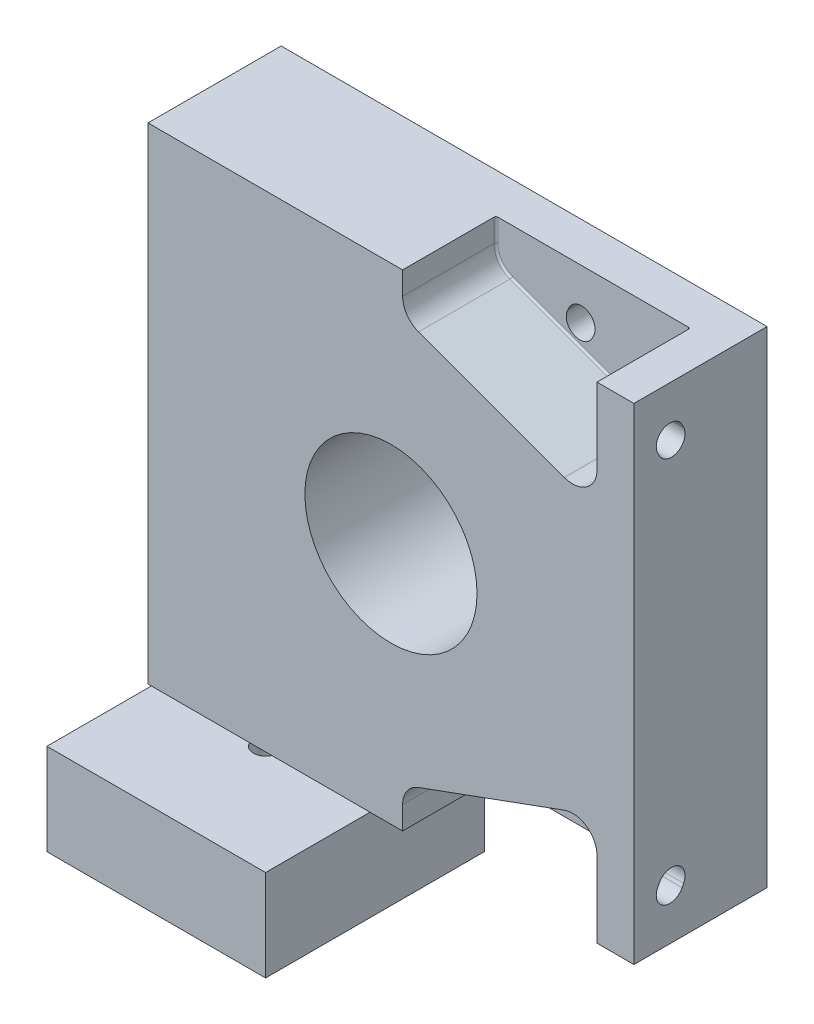
SolidWorks part; units mm, degrees
ref_plane "Front" through (0, 0, 0) normal (0, 0, 1) x (1, 0, 0)
ref_plane "Top" through (0, 0, 0) normal (0, 1, 0) x (1, 0, 0)
ref_plane "Right" through (0, 0, 0) normal (1, 0, 0) x (0, 0, -1)
sketch "Sketch2" plane through (0, 0, 0) normal (0, 0, 1) x (1, 0, 0)
  line L0 (-63.5, 63.5) -> (63.5, -63.5) construction
  line L1 (-63.5, 63.5) -> (63.5, 63.5)
  line L2 (-63.5, 63.5) -> (-63.5, -63.5)
  line L3 (-63.5, -63.5) -> (63.5, -63.5)
  line L4 (63.5, 63.5) -> (63.5, -63.5)
  dimension "D1" = 127
  dimension "D2" = 127
extrude "HOUSING" add sketch "Sketch2" along normal blind 39.5
ref_plane "Plane1" through (0, 0, 48.26) normal (0, 0, 1) x (1, 0, 0)
sketch "Sketch3" plane through (0, 0, 48.26) normal (0, 0, 1) x (1, 0, 0)
  circle A0 centre (0, 0) radius 22.5
  dimension "D1" = 45
sketch "Sketch4" plane through (0, 0, 39.5) normal (0, 0, 1) x (1, 0, 0)
  circle A0 centre (0, 0) radius 45.974
  dimension "D1" = 91.948
extrude "Cut-Extrude2" cut sketch "Sketch4" against normal blind 4.698 flip side to cut
sketch "Sketch8" plane through (0, 0, 34.802) normal (0, 0, 1) x (1, 0, 0)
  line L0 (3.048, -63.5) -> (3.048, -57.528)
  line L1 (-63.5, -63.5) -> (63.5, -63.5) construction
  line L2 (7.2207, -51.5629) -> (45.3207, -37.6564)
  line L3 (53.848, -43.6215) -> (53.848, -63.5)
  line L4 (-63.5, 63.5) -> (-63.5, -63.5) construction
  line L5 (3.048, -63.5) -> (53.848, -63.5)
  line L6 (0, 0) -> (83.0961, 0) construction
  line L7 (3.048, 63.5) -> (53.848, 63.5)
  line L8 (53.848, 43.6215) -> (53.848, 63.5)
  line L9 (7.2207, 51.5629) -> (45.3207, 37.6564)
  line L10 (3.048, 63.5) -> (3.048, 57.528)
  line L11 (53.848, -51.1628) -> (53.848, -17.132) construction
  line L12 (3.048, -53.086) -> (67.489, -29.5651) construction
  line L13 (3.048, -61.8074) -> (3.048, -48.2133) construction
  arc A0 (3.048, -57.528) -> (7.2207, -51.5629) centre (9.398, -57.528) cw
  arc A1 (45.3207, -37.6564) -> (53.848, -43.6215) centre (47.498, -43.6215) cw
  arc A2 (45.3207, 37.6564) -> (53.848, 43.6215) centre (47.498, 43.6215) ccw
  arc A3 (3.048, 57.528) -> (7.2207, 51.5629) centre (9.398, 57.528) ccw
  point P27 (53.848, -34.544)
  point P30 (3.048, -53.086)
  dimension "D1" = 6.35
  dimension "D2" = 50.8
  dimension "D3" = 66.548
  dimension "D4" = 28.956
  dimension "D5" = 10.414
extrude "MOUNTING POCKETS" cut sketch "Sketch8" against normal blind 24.384
sketch "Sketch21" plane through (63.5, -23.6461, 1.1666) normal (1, 0, 0) x (0, 0, -1)
  line L0 (1.1666, 111.3134) -> (1.1666, 5.23) construction
  line L1 (-54.2716, 23.6461) -> (63.3306, 23.6461) construction
  line L2 (-20.6415, 75.2421) -> (-21.0415, 76.0421)
  line L3 (-27.0254, 72.0502) -> (-27.4254, 72.8502)
  line L4 (1.1666, -39.8539) -> (1.1666, 87.1461) construction
  line L5 (-27.0254, -24.7579) -> (-27.4254, -25.5579)
  line L6 (-20.6415, -27.9498) -> (-21.0415, -28.7498)
  arc A0 (-21.0415, 76.0421) -> (-27.4254, 72.8502) centre (-24.2334, 74.4461) ccw
  arc A1 (-27.0254, 72.0502) -> (-20.6415, 75.2421) centre (-23.8334, 73.6461) ccw
  arc A2 (-27.0254, -24.7579) -> (-20.6415, -27.9498) centre (-23.8334, -26.3539) cw
  arc A3 (-21.0415, -28.7498) -> (-27.4254, -25.5579) centre (-24.2334, -27.1539) cw
  dimension "HORIZ METRIC DIST" = 25
  dimension "HORIZ ENG DIST" = 25.4
  dimension "VERTICAL METRIC DIST" = 50
  dimension "VERT ENG DIST" = 50.8
extrude "ENG_METRIC SLOT VERTICAL" cut sketch "Sketch21" against normal up to next
sketch "Sketch212" plane through (34.0621, -104.656, 0) normal (0, 0, -1) x (-1, 0, 0)
  line L0 (34.0621, 192.3232) -> (34.0621, 86.2399) construction
  line L1 (-54.2716, 104.656) -> (63.3306, 104.656) construction
  line L2 (12.254, 156.252) -> (11.854, 157.052)
  line L3 (5.8701, 153.06) -> (5.4701, 153.86)
  line L4 (5.8701, 56.252) -> (5.4701, 55.452)
  line L5 (12.254, 53.06) -> (11.854, 52.26)
  arc A0 (11.854, 157.052) -> (5.4701, 153.86) centre (8.6621, 155.456) ccw
  arc A1 (5.8701, 153.06) -> (12.254, 156.252) centre (9.0621, 154.656) ccw
  arc A2 (5.8701, 56.252) -> (12.254, 53.06) centre (9.0621, 54.656) cw
  arc A3 (11.854, 52.26) -> (5.4701, 55.452) centre (8.6621, 53.856) cw
  dimension "HORIZ METRIC DIST" = 25
  dimension "HORIZ ENG DIST" = 25.4
  dimension "VERTICAL METRIC DIST" = 50
  dimension "VERT ENG DIST" = 50.8
extrude "ENG_METRIC SLOT HORIZONTAL" cut sketch "Sketch212" against normal through all
fillet "Fillet3" radius 0.508 10 edges at (53.848, 53.5608, 10.418) (51.1378, 38.4182, 10.418) (26.2707, 44.6097, 10.418) (4.1947, 53.8882, 10.418) (3.048, 60.514, 10.418) (53.848, -53.5608, 10.418) (51.1378, -38.4182, 10.418) (26.2707, -44.6097, 10.418) (4.1947, -53.8882, 10.418) (3.048, -60.514, 10.418)
sketch "Sketch213" plane through (0, -63.5, 0) normal (0, -1, 0) x (1, 0, 0)
  line L0 (-63.5, 0) -> (63.5, 0) construction
  line L1 (-65.659, 1.905) -> (-8.509, 1.905)
  line L2 (-65.659, 1.905) -> (-65.659, 59.055)
  line L3 (-65.659, 59.055) -> (-8.509, 59.055)
  line L4 (-8.509, 1.905) -> (-8.509, 59.055)
  dimension "D1" = 57.15
  dimension "D2" = 57.15
  dimension "D3" = 1.905
  dimension "D4" = 8.509
extrude "Extrude1" add sketch "Sketch213" along normal blind 26.924
sketch "Sketch214" plane through (0, -90.424, 0) normal (0, -1, 0) x (1, 0, 0)
  line L0 (-65.659, 1.905) -> (-8.509, 1.905) construction
  line L1 (-65.659, 59.055) -> (-65.659, 1.905) construction
  circle A0 centre (-37.084, 30.48) radius 23.8125
  dimension "D3" = 47.625
  dimension "D1" = 28.575
  dimension "D2" = 28.575
extrude "Cut-Extrude3" cut sketch "Sketch214" against normal blind 5
sketch "Sketch215" plane through (0, -85.424, 0) normal (0, -1, 0) x (1, 0, 0)
  circle A0 centre (-37.084, 30.48) radius 3.175
  circle A1 centre (-37.084, 30.48) radius 23.8125 construction
  dimension "D1" = 6.35
extrude "Cut-Extrude4" cut sketch "Sketch215" against normal up to surface (21.924 mm away) up to face at (12.8058, -63.5, 15.458)
sketch "Sketch216" plane through (-65.659, 0, 0) normal (-1, 0, 0) x (0, 0, 1)
  line L1 (59.055, -63.5) -> (16.51, -63.5)
  line L2 (59.055, -63.5) -> (59.055, -66.548)
  line L3 (59.055, -66.548) -> (16.51, -66.548)
  line L4 (16.51, -63.5) -> (16.51, -66.548)
  dimension "D1" = 3.048
extrude "Cut-Extrude5" cut sketch "Sketch216" against normal up to next
hole_wizard "#8-32 Tapped Hole1" positions "Sketch218" profile "Sketch217" tap size "#8-32" standard "Ansi Inch"
sketch "Sketch218" plane through (0, -90.424, 0) normal (0, -1, 0) x (1, 0, 0)
  line L0 (-37.084, 30.48) -> (-37.084, 29.6778) construction
  line L1 (-19.7801, 30.48) -> (-37.084, 30.48) construction
  circle A0 centre (-37.084, 30.48) radius 3.175 construction
  point P0 (-60.706, 6.858)
  point P7 (-60.706, 54.102)
  point P8 (-13.462, 54.102)
  point P9 (-13.462, 6.858)
  dimension "D1" = 23.622
  dimension "D2" = 23.622
sketch "Sketch217" plane through (-60.706, -90.424, 6.858) normal (1, 0, 0) x (0, 0, -1)
  line L0 (0, 0) -> (0, 11.7464)
  line L1 (0, 11.7464) -> (1.7272, 10.7086)
  line L2 (1.7272, 10.7086) -> (1.7272, 0)
  line L5 (1.7272, 0) -> (0, 0)
  line L10 (0, 11.7464) -> (-1.7272, 10.7086) construction
  line L11 (0, -6.35) -> (0, 107.95) construction
  dimension "Tap Drill Dia." = 3.4544
  dimension "Tap Drill Depth" = 10.7086
  dimension "Drill Angle" = 118
cosmetic thread "Cosmetic Thread1" parameters "D1"=8.3312, "D2"=4.1656
sketch "Sketch239" plane through (-63.5, -121.6811, -83.5661) normal (-1, 0, 0) x (0, 0, 1)
  line L0 (102.3006, 124.3698) -> (102.3006, 122.0362)
  line L1 (101.5379, 121.2735) -> (100.4208, 121.2735)
  line L2 (99.6339, 122.0604) -> (99.6339, 124.195)
  line L3 (100.4552, 125.0162) -> (101.5379, 125.0162)
  line L4 (101.6546, 123.1805) -> (101.6546, 122.3531)
  line L5 (101.4072, 122.1057) -> (100.5491, 122.1057)
  line L6 (100.3049, 122.3499) -> (100.3049, 123.8847)
  line L7 (100.5701, 124.1499) -> (101.4117, 124.1499)
  line L8 (101.659, 123.901) -> (101.6546, 123.1805)
  line L9 (101.6214, 127.7512) -> (101.6214, 126.2045)
  line L10 (101.4803, 126.0635) -> (101.1416, 126.0635)
  line L11 (100.9953, 126.2098) -> (100.9953, 127.7512)
  line L12 (100.9953, 127.7512) -> (101.6214, 127.7512)
  line L13 (102.3006, 128.5943) -> (102.3006, 125.7347)
  line L14 (101.7926, 125.2267) -> (101.2545, 125.2267)
  line L15 (99.6339, 125.2267) -> (99.6339, 126.0693)
  line L16 (99.6339, 126.0693) -> (100.1002, 126.0693)
  line L17 (100.3288, 126.2979) -> (100.3288, 127.7582)
  line L18 (100.3288, 127.7582) -> (99.6339, 127.7582)
  line L19 (99.6339, 127.7582) -> (99.6339, 128.5943)
  line L20 (99.6339, 128.5943) -> (102.3006, 128.5943)
  line L21 (101.3052, 111.8683) -> (101.3052, 111.033)
  line L22 (101.3052, 111.033) -> (101.7294, 111.033)
  line L23 (102.3006, 111.6043) -> (102.3006, 113.7376)
  line L24 (101.5923, 114.4459) -> (100.3232, 114.4459)
  line L25 (99.6339, 113.7566) -> (99.6339, 111.4732)
  line L26 (100.1192, 110.9879) -> (100.6227, 110.9879)
  line L27 (100.6227, 110.9879) -> (100.6227, 111.8368)
  line L28 (100.6227, 111.8368) -> (100.4696, 111.8368)
  line L29 (100.2358, 112.0705) -> (100.2358, 113.3006)
  line L30 (100.5426, 113.6074) -> (101.3217, 113.6074)
  line L31 (101.6185, 113.3107) -> (101.6185, 112.0939)
  line L32 (101.3929, 111.8683) -> (101.3052, 111.8683)
  line L33 (99.6339, 136.1587) -> (102.3006, 134.699)
  line L34 (102.3006, 134.699) -> (102.3006, 133.4017)
  line L35 (102.3006, 133.4017) -> (99.6339, 131.9711)
  line L36 (99.6339, 131.9711) -> (99.6339, 132.9287)
  line L37 (99.6339, 132.9287) -> (100.0922, 133.1628)
  line L38 (100.0922, 133.1628) -> (100.0922, 134.9283)
  line L39 (100.0922, 134.9283) -> (99.6339, 135.1676)
  line L40 (99.6339, 135.1676) -> (99.6339, 136.1587)
  line L41 (100.7046, 134.6309) -> (100.7046, 133.468)
  line L42 (100.7046, 133.468) -> (101.6586, 133.9731)
  line L43 (101.6586, 133.9731) -> (101.6586, 134.1258)
  line L44 (101.6586, 134.1258) -> (100.7046, 134.6309)
  line L45 (102.3006, 131.8571) -> (102.3006, 128.8708)
  line L46 (102.3006, 128.8708) -> (101.6626, 128.8708)
  line L47 (101.6626, 128.8708) -> (101.6626, 131.0623)
  line L48 (101.6626, 131.0623) -> (101.2925, 131.0623)
  line L49 (101.2925, 131.0623) -> (101.2925, 128.9844)
  line L50 (101.2925, 128.9844) -> (100.693, 128.9844)
  line L51 (100.693, 128.9844) -> (100.693, 131.0623)
  line L52 (100.693, 131.0623) -> (100.2774, 131.0623)
  line L53 (100.2774, 131.0623) -> (100.2774, 128.8708)
  line L54 (100.2774, 128.8708) -> (99.6339, 128.8708)
  line L55 (99.6339, 128.8708) -> (99.6339, 131.8571)
  line L56 (99.6339, 131.8571) -> (102.3006, 131.8571)
  line L57 (102.3006, 121.1265) -> (102.3006, 117.8159)
  line L58 (102.3006, 117.8159) -> (101.6106, 117.8159)
  line L59 (101.6106, 117.8159) -> (101.6106, 119.0485)
  line L60 (101.6106, 119.0485) -> (99.6339, 119.0485)
  line L61 (99.6339, 119.0485) -> (99.6339, 119.9334)
  line L62 (99.6339, 119.9334) -> (101.6102, 119.9334)
  line L63 (101.6102, 119.9334) -> (101.6102, 121.1265)
  line L64 (101.6102, 121.1265) -> (102.3006, 121.1265)
  line L65 (102.3006, 117.6536) -> (102.3006, 114.6497)
  line L66 (102.3006, 114.6497) -> (101.6621, 114.6497)
  line L67 (101.6621, 114.6497) -> (101.6621, 116.8274)
  line L68 (101.6621, 116.8274) -> (101.2997, 116.8274)
  line L69 (101.2997, 116.8274) -> (101.2997, 114.7563)
  line L70 (101.2997, 114.7563) -> (100.6993, 114.7563)
  line L71 (100.6993, 114.7563) -> (100.6993, 116.8274)
  line L72 (100.6993, 116.8274) -> (100.2804, 116.8274)
  line L73 (100.2804, 116.8274) -> (100.2804, 114.6497)
  line L74 (100.2804, 114.6497) -> (99.6339, 114.6497)
  line L75 (99.6339, 114.6497) -> (99.6339, 117.6536)
  line L76 (99.6339, 117.6536) -> (102.3006, 117.6536)
  line L77 (102.3006, 110.7071) -> (102.3006, 109.8385)
  line L78 (102.3006, 109.8385) -> (101.3454, 109.8385)
  line L79 (101.3454, 109.8385) -> (101.3454, 108.0035)
  line L80 (101.3454, 108.0035) -> (102.3006, 108.0035)
  line L81 (102.3006, 108.0035) -> (102.3006, 107.1132)
  line L82 (102.3006, 107.1132) -> (99.6339, 107.1132)
  line L83 (99.6339, 107.1132) -> (99.6339, 108.0035)
  line L84 (99.6339, 108.0035) -> (100.5967, 108.0035)
  line L85 (100.5967, 108.0035) -> (100.5967, 109.8385)
  line L86 (100.5967, 109.8385) -> (99.6339, 109.8385)
  line L87 (99.6339, 109.8385) -> (99.6339, 110.7071)
  line L88 (99.6339, 110.7071) -> (102.3006, 110.7071)
  line L89 (98.9126, 131.6685) -> (98.9126, 128.6152)
  line L90 (98.9126, 128.6152) -> (91.9852, 121.7251)
  line L91 (91.9852, 121.7251) -> (96.8043, 116.8798)
  line L92 (96.8043, 116.8798) -> (96.8043, 124.7941)
  line L93 (96.8043, 124.7941) -> (98.9126, 126.8817)
  line L94 (98.9126, 126.8817) -> (98.9126, 111.5851)
  line L95 (98.9126, 111.5851) -> (88.8711, 121.6811)
  line L96 (88.8711, 121.6811) -> (98.9126, 131.6685)
  line L97 (103.0216, 131.6685) -> (113.0631, 121.6811)
  line L98 (113.0631, 121.6811) -> (103.0216, 111.5851)
  line L99 (103.0216, 131.6685) -> (103.0216, 128.6152)
  line L100 (103.0216, 128.6152) -> (109.985, 121.6893)
  line L101 (109.985, 121.6893) -> (105.1659, 116.844)
  line L102 (105.1659, 116.844) -> (105.1659, 124.7583)
  line L103 (105.1659, 124.7583) -> (103.0216, 126.8089)
  line L104 (103.0216, 126.8089) -> (103.0216, 111.5851)
  line L105 (100.3283, 125.2267) -> (99.6339, 125.2267)
  line L106 (118.3681, 121.6811) -> (83.5661, 121.6811) construction
  line L107 (118.3681, 75.7071) -> (118.3681, 167.6551) construction
  line L108 (113.0631, 121.6811) -> (88.8711, 121.6811) construction
  arc A0 (102.3006, 122.0362) -> (101.5379, 121.2735) centre (101.5379, 122.0362) cw
  arc A1 (100.4208, 121.2735) -> (99.6339, 122.0604) centre (100.4208, 122.0604) cw
  arc A2 (99.6339, 124.195) -> (100.4552, 125.0162) centre (100.4552, 124.195) cw
  arc A3 (101.5379, 125.0162) -> (102.3006, 124.3698) centre (101.5379, 124.2431) cw
  arc A4 (101.6546, 122.3531) -> (101.4072, 122.1057) centre (101.4072, 122.3531) cw
  arc A5 (100.5491, 122.1057) -> (100.3049, 122.3499) centre (100.5491, 122.3499) cw
  arc A6 (100.3049, 123.8847) -> (100.5701, 124.1499) centre (100.5701, 123.8847) cw
  arc A7 (101.4117, 124.1499) -> (101.659, 123.901) centre (101.4117, 123.9025) cw
  arc A8 (101.6214, 126.2045) -> (101.4803, 126.0635) centre (101.4803, 126.2045) cw
  arc A9 (101.1416, 126.0635) -> (100.9953, 126.2098) centre (101.1416, 126.2098) cw
  arc A10 (100.1002, 126.0693) -> (100.3288, 126.2979) centre (100.1002, 126.2979) ccw
  arc A11 (101.7926, 125.2267) -> (102.3006, 125.7347) centre (101.7926, 125.7347) ccw
  arc A12 (101.2545, 125.2267) -> (100.7973, 125.6839) centre (101.2545, 125.6839) cw
  arc A13 (100.7973, 125.6839) -> (100.3283, 125.2267) centre (100.34, 125.6839) cw
  arc A14 (101.7294, 111.033) -> (102.3006, 111.6043) centre (101.7294, 111.6043) ccw
  arc A15 (102.3006, 113.7376) -> (101.5923, 114.4459) centre (101.5923, 113.7376) ccw
  arc A16 (100.3232, 114.4459) -> (99.6339, 113.7566) centre (100.3232, 113.7566) ccw
  arc A17 (99.6339, 111.4732) -> (100.1192, 110.9879) centre (100.1192, 111.4732) ccw
  arc A18 (100.4696, 111.8368) -> (100.2358, 112.0705) centre (100.4696, 112.0705) cw
  arc A19 (100.2358, 113.3006) -> (100.5426, 113.6074) centre (100.5426, 113.3006) cw
  arc A20 (101.3217, 113.6074) -> (101.6185, 113.3107) centre (101.3217, 113.3107) cw
  arc A21 (101.6185, 112.0939) -> (101.3929, 111.8683) centre (101.3929, 112.0939) cw
extrude "AEROTECH5" [suppressed] cut sketch "Sketch239" against normal blind 0.1
sketch "Sketch240" plane through (80.6623, 63.5, -107.4581) normal (0, 1, 0) x (-1, 0, 0)
  line L0 (108.1996, 126.0312) -> (110.5333, 126.0312)
  line L1 (111.2959, 125.2686) -> (111.2959, 124.1515)
  line L2 (110.509, 123.3646) -> (108.3744, 123.3646)
  line L3 (107.5532, 124.1858) -> (107.5532, 125.2685)
  line L4 (109.3889, 125.3852) -> (110.2163, 125.3852)
  line L5 (110.4637, 125.1378) -> (110.4637, 124.2797)
  line L6 (110.2195, 124.0355) -> (108.6847, 124.0355)
  line L7 (108.4195, 124.3007) -> (108.4195, 125.1423)
  line L8 (108.6684, 125.3896) -> (109.3889, 125.3852)
  line L9 (104.8182, 125.352) -> (106.3649, 125.352)
  line L10 (106.5059, 125.211) -> (106.5059, 124.8722)
  line L11 (106.3597, 124.726) -> (104.8182, 124.726)
  line L12 (104.8182, 124.726) -> (104.8182, 125.352)
  line L13 (103.9751, 126.0312) -> (106.8348, 126.0312)
  line L14 (107.3428, 125.5232) -> (107.3428, 124.9851)
  line L15 (107.3428, 123.3646) -> (106.5001, 123.3646)
  line L16 (106.5001, 123.3646) -> (106.5001, 123.8308)
  line L17 (106.2715, 124.0594) -> (104.8112, 124.0594)
  line L18 (104.8112, 124.0594) -> (104.8112, 123.3646)
  line L19 (104.8112, 123.3646) -> (103.9751, 123.3646)
  line L20 (103.9751, 123.3646) -> (103.9751, 126.0312)
  line L21 (120.7011, 125.0358) -> (121.5364, 125.0358)
  line L22 (121.5364, 125.0358) -> (121.5364, 125.46)
  line L23 (120.9652, 126.0312) -> (118.8318, 126.0312)
  line L24 (118.1235, 125.3229) -> (118.1235, 124.0538)
  line L25 (118.8128, 123.3646) -> (121.0962, 123.3646)
  line L26 (121.5815, 123.8498) -> (121.5815, 124.3533)
  line L27 (121.5815, 124.3533) -> (120.7327, 124.3533)
  line L28 (120.7327, 124.3533) -> (120.7327, 124.2002)
  line L29 (120.4989, 123.9664) -> (119.2688, 123.9664)
  line L30 (118.962, 124.2732) -> (118.962, 125.0523)
  line L31 (119.2587, 125.3491) -> (120.4755, 125.3491)
  line L32 (120.7011, 125.1235) -> (120.7011, 125.0358)
  line L33 (96.4107, 123.3646) -> (97.8704, 126.0312)
  line L34 (97.8704, 126.0312) -> (99.1677, 126.0312)
  line L35 (99.1677, 126.0312) -> (100.5983, 123.3646)
  line L36 (100.5983, 123.3646) -> (99.6408, 123.3646)
  line L37 (99.6408, 123.3646) -> (99.4066, 123.8228)
  line L38 (99.4066, 123.8228) -> (97.6412, 123.8228)
  line L39 (97.6412, 123.8228) -> (97.4018, 123.3646)
  line L40 (97.4018, 123.3646) -> (96.4107, 123.3646)
  line L41 (97.9385, 124.4352) -> (99.1014, 124.4352)
  line L42 (99.1014, 124.4352) -> (98.5963, 125.3892)
  line L43 (98.5963, 125.3892) -> (98.4436, 125.3892)
  line L44 (98.4436, 125.3892) -> (97.9385, 124.4352)
  line L45 (100.7123, 126.0312) -> (103.6986, 126.0312)
  line L46 (103.6986, 126.0312) -> (103.6986, 125.3933)
  line L47 (103.6986, 125.3933) -> (101.5071, 125.3933)
  line L48 (101.5071, 125.3933) -> (101.5071, 125.0231)
  line L49 (101.5071, 125.0231) -> (103.585, 125.0231)
  line L50 (103.585, 125.0231) -> (103.585, 124.4236)
  line L51 (103.585, 124.4236) -> (101.5071, 124.4236)
  line L52 (101.5071, 124.4236) -> (101.5071, 124.008)
  line L53 (101.5071, 124.008) -> (103.6986, 124.008)
  line L54 (103.6986, 124.008) -> (103.6986, 123.3646)
  line L55 (103.6986, 123.3646) -> (100.7123, 123.3646)
  line L56 (100.7123, 123.3646) -> (100.7123, 126.0312)
  line L57 (111.4429, 126.0312) -> (114.7535, 126.0312)
  line L58 (114.7535, 126.0312) -> (114.7535, 125.3412)
  line L59 (114.7535, 125.3412) -> (113.5209, 125.3412)
  line L60 (113.5209, 125.3412) -> (113.5209, 123.3646)
  line L61 (113.5209, 123.3646) -> (112.636, 123.3646)
  line L62 (112.636, 123.3646) -> (112.636, 125.3408)
  line L63 (112.636, 125.3408) -> (111.4429, 125.3408)
  line L64 (111.4429, 125.3408) -> (111.4429, 126.0312)
  line L65 (114.9158, 126.0312) -> (117.9197, 126.0312)
  line L66 (117.9197, 126.0312) -> (117.9197, 125.3927)
  line L67 (117.9197, 125.3927) -> (115.742, 125.3927)
  line L68 (115.742, 125.3927) -> (115.742, 125.0303)
  line L69 (115.742, 125.0303) -> (117.8131, 125.0303)
  line L70 (117.8131, 125.0303) -> (117.8131, 124.43)
  line L71 (117.8131, 124.43) -> (115.742, 124.43)
  line L72 (115.742, 124.43) -> (115.742, 124.0111)
  line L73 (115.742, 124.0111) -> (117.9197, 124.0111)
  line L74 (117.9197, 124.0111) -> (117.9197, 123.3646)
  line L75 (117.9197, 123.3646) -> (114.9158, 123.3646)
  line L76 (114.9158, 123.3646) -> (114.9158, 126.0312)
  line L77 (121.8623, 126.0312) -> (122.7309, 126.0312)
  line L78 (122.7309, 126.0312) -> (122.7309, 125.076)
  line L79 (122.7309, 125.076) -> (124.5659, 125.076)
  line L80 (124.5659, 125.076) -> (124.5659, 126.0312)
  line L81 (124.5659, 126.0312) -> (125.4563, 126.0312)
  line L82 (125.4563, 126.0312) -> (125.4563, 123.3646)
  line L83 (125.4563, 123.3646) -> (124.5659, 123.3646)
  line L84 (124.5659, 123.3646) -> (124.5659, 124.3273)
  line L85 (124.5659, 124.3273) -> (122.7309, 124.3273)
  line L86 (122.7309, 124.3273) -> (122.7309, 123.3646)
  line L87 (122.7309, 123.3646) -> (121.8623, 123.3646)
  line L88 (121.8623, 123.3646) -> (121.8623, 126.0312)
  line L89 (100.9009, 122.6432) -> (103.9543, 122.6432)
  line L90 (103.9543, 122.6432) -> (110.8443, 115.7158)
  line L91 (110.8443, 115.7158) -> (115.6896, 120.535)
  line L92 (115.6896, 120.535) -> (107.7753, 120.535)
  line L93 (107.7753, 120.535) -> (105.6877, 122.6432)
  line L94 (105.6877, 122.6432) -> (120.9843, 122.6432)
  line L95 (120.9843, 122.6432) -> (110.8883, 112.6017)
  line L96 (110.8883, 112.6017) -> (100.9009, 122.6432)
  line L97 (100.9009, 126.7523) -> (110.8883, 136.7938)
  line L98 (110.8883, 136.7938) -> (120.9843, 126.7523)
  line L99 (100.9009, 126.7523) -> (103.9543, 126.7523)
  line L100 (103.9543, 126.7523) -> (110.8801, 133.7157)
  line L101 (110.8801, 133.7157) -> (115.7254, 128.8965)
  line L102 (115.7254, 128.8965) -> (107.8111, 128.8965)
  line L103 (107.8111, 128.8965) -> (105.7606, 126.7523)
  line L104 (105.7606, 126.7523) -> (120.9843, 126.7523)
  line L105 (107.3428, 124.059) -> (107.3428, 123.3646)
  line L106 (110.8883, 136.7938) -> (110.8883, 112.6017) construction
  line L107 (110.8883, 142.2601) -> (110.8883, 107.4581) construction
  line L108 (77.6143, 142.2601) -> (144.1623, 142.2601) construction
  line L109 (17.1623, 107.4581) -> (144.1623, 107.4581) construction
  arc A0 (110.5333, 126.0312) -> (111.2959, 125.2686) centre (110.5333, 125.2686) cw
  arc A1 (111.2959, 124.1515) -> (110.509, 123.3646) centre (110.509, 124.1515) cw
  arc A2 (108.3744, 123.3646) -> (107.5532, 124.1858) centre (108.3744, 124.1858) cw
  arc A3 (107.5532, 125.2685) -> (108.1996, 126.0312) centre (108.3264, 125.2685) cw
  arc A4 (110.2163, 125.3852) -> (110.4637, 125.1378) centre (110.2163, 125.1378) cw
  arc A5 (110.4637, 124.2797) -> (110.2195, 124.0355) centre (110.2195, 124.2797) cw
  arc A6 (108.6847, 124.0355) -> (108.4195, 124.3007) centre (108.6847, 124.3007) cw
  arc A7 (108.4195, 125.1423) -> (108.6684, 125.3896) centre (108.6669, 125.1423) cw
  arc A8 (106.3649, 125.352) -> (106.5059, 125.211) centre (106.3649, 125.211) cw
  arc A9 (106.5059, 124.8722) -> (106.3597, 124.726) centre (106.3597, 124.8722) cw
  arc A10 (106.5001, 123.8308) -> (106.2715, 124.0594) centre (106.2715, 123.8308) ccw
  arc A11 (107.3428, 125.5232) -> (106.8348, 126.0312) centre (106.8348, 125.5232) ccw
  arc A12 (107.3428, 124.9851) -> (106.8856, 124.5279) centre (106.8856, 124.9851) cw
  arc A13 (106.8856, 124.5279) -> (107.3428, 124.059) centre (106.8856, 124.0706) cw
  arc A14 (121.5364, 125.46) -> (120.9652, 126.0312) centre (120.9652, 125.46) ccw
  arc A15 (118.8318, 126.0312) -> (118.1235, 125.3229) centre (118.8318, 125.3229) ccw
  arc A16 (118.1235, 124.0538) -> (118.8128, 123.3646) centre (118.8128, 124.0538) ccw
  arc A17 (121.0962, 123.3646) -> (121.5815, 123.8498) centre (121.0962, 123.8498) ccw
  arc A18 (120.7327, 124.2002) -> (120.4989, 123.9664) centre (120.4989, 124.2002) cw
  arc A19 (119.2688, 123.9664) -> (118.962, 124.2732) centre (119.2688, 124.2732) cw
  arc A20 (118.962, 125.0523) -> (119.2587, 125.3491) centre (119.2587, 125.0523) cw
  arc A21 (120.4755, 125.3491) -> (120.7011, 125.1235) centre (120.4755, 125.1235) cw
extrude "Cut-Extrude6" [suppressed] cut sketch "Sketch240" against normal blind 0.1
sketch "Sketch241" plane through (0, 0, 39.5) normal (0, 0, 1) x (1, 0, 0)
  circle A0 centre (0, 0) radius 45.974
  circle A1 centre (0, 0) radius 45.974 construction
extrude "Cut-Extrude7" cut sketch "Sketch241" against normal up to surface (4.698 mm away) up to face at (20.8684, 0, 34.802)
extrude "Cut-Extrude8" cut sketch "Sketch3" against normal through all
ref_axis "Axis1" through (0, 0, -2.9527) along (0, 0, 1)
ref_plane "Plane2" through (0, 0, 0) normal (0, 1, 0) x (0, 0, 1)
